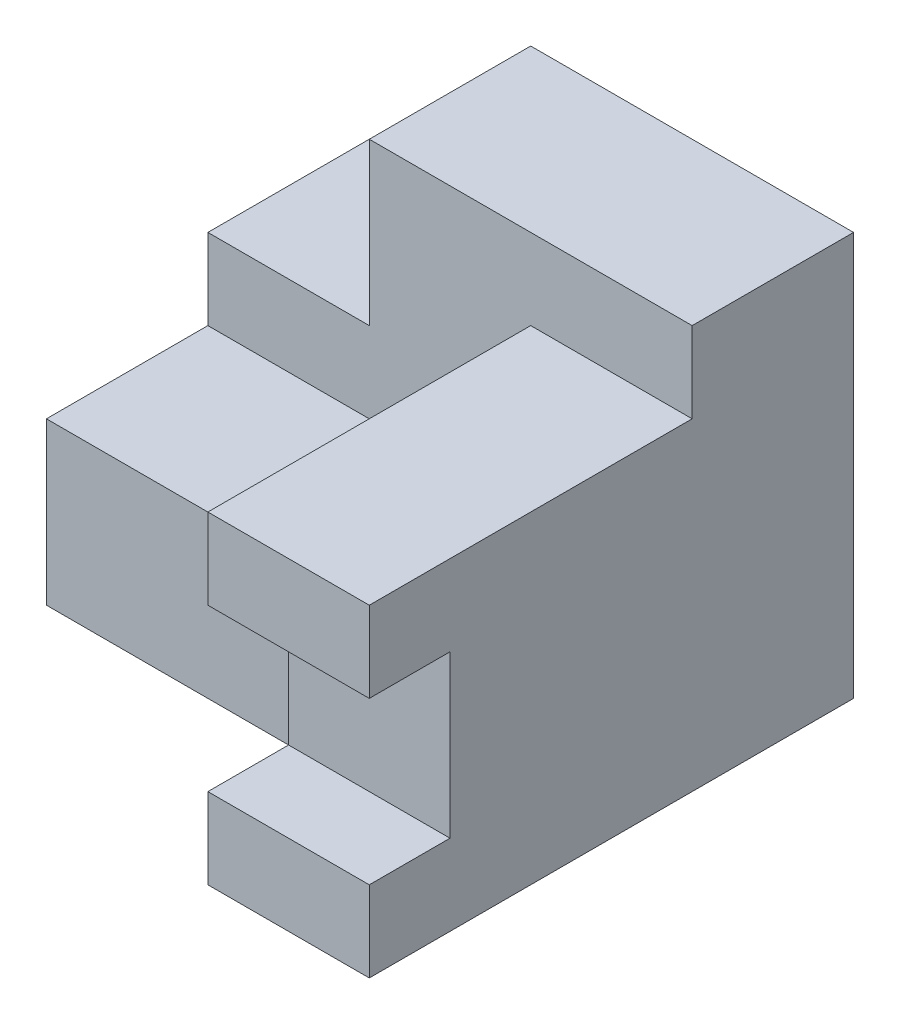
SolidWorks part; units mm, degrees
ref_plane "Front Plane" through (0, 0, 0) normal (0, 0, 1) x (1, 0, 0)
ref_plane "Top Plane" through (0, 0, 0) normal (0, 1, 0) x (1, 0, 0)
ref_plane "Right Plane" through (0, 0, 0) normal (1, 0, 0) x (0, 0, -1)
sketch "Sketch1" plane through (0, 0, 0) normal (0, 0, 1) x (1, 0, 0)
  line L0 (120, -60) -> (40, -60)
  line L1 (-120, -100) -> (120, -100)
  line L2 (-120, -100) -> (-120, 100)
  line L3 (-120, 100) -> (120, 100)
  line L4 (120, -100) -> (120, 100)
  line L5 (-120, -100) -> (120, 100) construction
  line L6 (-120, 100) -> (120, -100) construction
  line L7 (40, -60) -> (40, -100)
  line L8 (40, -60) -> (40, 20)
  line L9 (40, 20) -> (120, 20)
  line L10 (40, 20) -> (40, 60)
  line L11 (40, 60) -> (120, 60)
  line L12 (40, -20) -> (-120, -20)
  line L13 (-120, 20) -> (-40, 20)
  line L14 (-40, 20) -> (-40, 100)
  point P0 (0, 0)
  dimension "D1" = 200
  dimension "D2" = 240
extrude "Boss-Extrude1" add sketch "Sketch1" along normal blind 120 contours L0 L7 L1 L4 region at (80, -80, 0)
extrude "Boss-Extrude2" add sketch "Sketch1<3>" along normal blind 40 contours L8 L12 L2 L1 L7 region at (-40, -60, 0)
sketch "Sketch1<3>" plane through (0, 0, 0) normal (0, 0, 1) x (1, 0, 0) same geometry as "Sketch1"
extrude "Boss-Extrude3" add sketch "Sketch1<4>" along normal blind 80 contours L9 L8 L0 L4 region at (80, -20, 0)
sketch "Sketch1<4>" plane through (0, 0, 0) normal (0, 0, 1) x (1, 0, 0) same geometry as "Sketch1"
extrude "Boss-Extrude4" add sketch "Sketch1<5>" along normal blind 120 contours L11 L10 L9 L4 region at (80, 40, 0)
sketch "Sketch1<5>" plane through (0, 0, 0) normal (0, 0, 1) x (1, 0, 0) same geometry as "Sketch1"
extrude "Boss-Extrude5" add sketch "Sketch1<6>" against normal blind 120 contours L11 L10 L9 L4 region at (80, 40, 0)
sketch "Sketch1<6>" plane through (0, 0, 0) normal (0, 0, 1) x (1, 0, 0) same geometry as "Sketch1"
extrude "Boss-Extrude6" add sketch "Sketch1<7>" against normal blind 120 contours L9 L8 L0 L4 region at (80, -20, 0)
sketch "Sketch1<7>" plane through (0, 0, 0) normal (0, 0, 1) x (1, 0, 0) same geometry as "Sketch1"
extrude "Boss-Extrude7" add sketch "Sketch1<8>" against normal blind 120 contours L0 L7 L1 L4 region at (80, -80, 0)
sketch "Sketch1<8>" plane through (0, 0, 0) normal (0, 0, 1) x (1, 0, 0) same geometry as "Sketch1"
extrude "Boss-Extrude8" add sketch "Sketch1<9>" against normal blind 120 contours L8 L12 L2 L1 L7 region at (-40, -60, 0)
sketch "Sketch1<9>" plane through (0, 0, 0) normal (0, 0, 1) x (1, 0, 0) same geometry as "Sketch1"
sketch "Sketch2" plane through (0, 60, 0) normal (0, 1, 0) x (1, 0, 0)
  line L0 (120, 40) -> (40, 40)
  line L1 (120, -120) -> (120, 120) construction
  line L2 (40, -40) -> (40, 120) construction
  line L3 (120, 120) -> (40, 120)
  line L4 (40, 120) -> (40, 40)
  line L5 (120, 120) -> (120, 40)
extrude "Boss-Extrude9" add sketch "Sketch2" along normal blind 40
sketch "Sketch3" plane through (40, 0, 0) normal (-1, 0, 0) x (0, 0, 1)
  line L0 (-40, 100) -> (-40, -20)
  line L1 (40, -20) -> (-120, -20) construction
  line L2 (-40, -20) -> (-120, -20)
  line L3 (-40, 100) -> (-120, 100)
  line L4 (-120, 100) -> (-120, -20)
extrude "Boss-Extrude10" add sketch "Sketch3" along normal blind 80
sketch "Sketch4" plane through (-40, 0, 0) normal (-1, 0, 0) x (0, 0, 1)
  line L0 (-40, 20) -> (-120, 20)
  line L1 (-40, -20) -> (-40, 60) construction
  line L2 (-120, 100) -> (-120, -20) construction
  line L3 (-120, 20) -> (-120, -20)
  line L4 (-120, -20) -> (-40, -20)
  line L5 (-40, -20) -> (-40, 20)
extrude "Boss-Extrude11" add sketch "Sketch4" along normal blind 80
